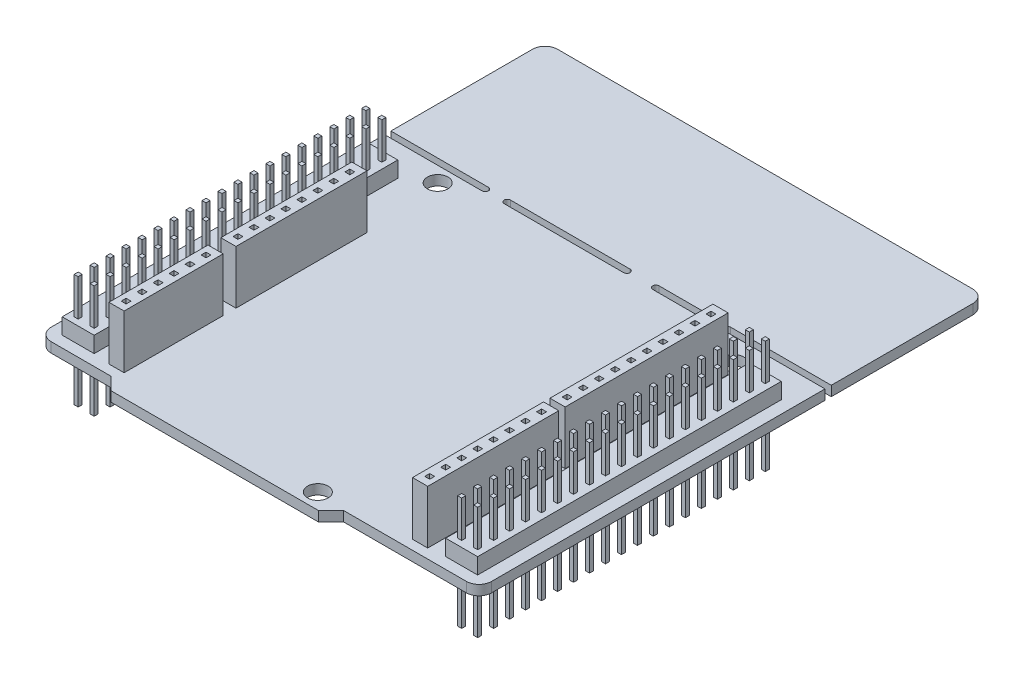
SolidWorks part; units mm, degrees
ref_plane "Front" through (0, 0, 0) normal (0, 0, 1) x (1, 0, 0)
ref_plane "Top" through (0, 0, 0) normal (0, 1, 0) x (1, 0, 0)
ref_plane "Right" through (0, 0, 0) normal (1, 0, 0) x (0, 0, -1)
ref_axis "X" through (-80.9, 0, 0) along (1, 0, 0)
ref_axis "Y" through (0, -50, 0) along (0, 1, 0)
ref_axis "Z" through (0, 0, -80.9) along (0, 0, 1)
sketch "Sketch1" plane through (0, 0, 0) normal (0, 1, 0) x (1, 0, 0)
  line L6 (6.06, 55.5) -> (-1.27, 55.5)
  line L7 (-1.27, 54.5) -> (6.06, 54.5)
  line L10 (-5.89, 55.5) -> (-24.89, 55.5)
  line L11 (-24.89, 54.5) -> (-5.89, 54.5)
  line L53 (24.11, 80) -> (-41.89, 80)
  line L54 (-43.89, 78) -> (-43.89, 55.5)
  line L55 (-43.89, 55.5) -> (-28.39, 55.5)
  line L56 (-28.39, 54.5) -> (-43.89, 54.5)
  line L57 (-43.89, 54.5) -> (-43.89, 1.5)
  line L58 (-41.89, -0.5) -> (-32.39, -0.5)
  line L59 (-32.39, -0.5) -> (-30.39, -2.5)
  line L60 (-30.39, -2.5) -> (2.61, -2.5)
  line L61 (2.61, -2.5) -> (4.61, -0.5)
  line L62 (4.61, -0.5) -> (24.11, -0.5)
  line L63 (26.11, 1.5) -> (26.11, 54.5)
  line L64 (26.11, 54.5) -> (10.11, 54.5)
  line L65 (10.11, 55.5) -> (26.11, 55.5)
  line L66 (26.11, 55.5) -> (26.11, 78)
  arc A21 (1.636, 0) -> (-1.636, 0) centre (0, 0) ccw
  arc A22 (-1.636, 0) -> (1.636, 0) centre (0, 0) ccw
  arc A31 (26.11, 78) -> (24.11, 80) centre (24.11, 78) ccw
  arc A32 (-41.89, 80) -> (-43.89, 78) centre (-41.89, 78) ccw
  arc A33 (-28.39, 54.5) -> (-28.39, 55.5) centre (-28.39, 55) ccw
  arc A34 (-43.89, 1.5) -> (-41.89, -0.5) centre (-41.89, 1.5) ccw
  arc A35 (24.11, -0.5) -> (26.11, 1.5) centre (24.11, 1.5) ccw
  arc A36 (9.61, 55) -> (10.11, 54.5) centre (10.11, 55) ccw
  arc A37 (10.11, 55.5) -> (9.61, 55) centre (10.11, 55) ccw
  arc A39 (16.876, 50.8) -> (13.604, 50.8) centre (15.24, 50.8) ccw
  arc A40 (13.604, 50.8) -> (16.876, 50.8) centre (15.24, 50.8) ccw
  arc A43 (-31.384, 52.07) -> (-34.656, 52.07) centre (-33.02, 52.07) ccw
  arc A44 (-34.656, 52.07) -> (-31.384, 52.07) centre (-33.02, 52.07) ccw
  arc A49 (6.06, 54.5) -> (6.06, 55.5) centre (6.06, 55) ccw
  arc A50 (-1.77, 55) -> (-1.27, 54.5) centre (-1.27, 55) ccw
  arc A51 (-1.27, 55.5) -> (-1.77, 55) centre (-1.27, 55) ccw
  arc A55 (-5.89, 54.5) -> (-5.89, 55.5) centre (-5.89, 55) ccw
  arc A56 (-25.39, 55) -> (-24.89, 54.5) centre (-24.89, 55) ccw
  arc A57 (-24.89, 55.5) -> (-25.39, 55) centre (-24.89, 55) ccw
extrude "Boss-Extrude1" add sketch "Sketch1" along normal mid plane 1.5802
sketch "Sketch2" plane through (0, 0.7901, 0) normal (0, 1, 0) x (1, 0, 0)
  line L0 (-41.9101, 49.5301) -> (-36.8301, 49.5301)
  line L1 (-36.8301, 49.5301) -> (-36.8301, 1.2701)
  line L2 (-36.8301, 1.2701) -> (-41.9101, 1.2701)
  line L3 (-41.9101, 1.2701) -> (-41.9101, 49.5301)
  line L4 (19.0499, 49.5301) -> (24.1299, 49.5301)
  line L5 (24.1299, 49.5301) -> (24.1299, 1.2701)
  line L6 (24.1299, 1.2701) -> (19.0499, 1.2701)
  line L7 (19.0499, 1.2701) -> (19.0499, 49.5301)
  line L8 (-43.89, 54.5) -> (-43.89, 1.5) construction
  line L14 (-41.89, -0.5) -> (-32.39, -0.5) construction
  dimension "D1" = 1.9799
  dimension "D2" = 5.08
  dimension "D3" = 48.26
  dimension "D4" = 55.88
  dimension "D5" = 1.7701
extrude "Boss-Extrude2" add sketch "Sketch2" along normal blind 2.5298
sketch "Sketch3" plane through (0, 3.3199, 0) normal (0, 1, 0) x (1, 0, 0)
  line L0 (-40.9576, 48.5776) -> (-40.3226, 48.5776)
  line L1 (-40.3226, 48.5776) -> (-40.3226, 47.9426)
  line L2 (-40.3226, 47.9426) -> (-40.9576, 47.9426)
  line L3 (-40.9576, 47.9426) -> (-40.9576, 48.5776)
  line L4 (20.0024, 48.5776) -> (20.6374, 48.5776)
  line L5 (20.0024, 48.5776) -> (20.0024, 47.9426)
  line L6 (20.0024, 47.9426) -> (20.6374, 47.9426)
  line L7 (20.6374, 47.9426) -> (20.6374, 48.5776)
  line L8 (-40.9576, 48.2601) -> (-40.6401, 48.2601) construction
  line L9 (-40.6401, 48.2601) -> (-40.6401, 48.5776) construction
  line L10 (20.3199, 48.5776) -> (20.3199, 48.2601) construction
  line L11 (20.3199, 48.2601) -> (20.0024, 48.2601) construction
  line L12 (-36.8301, 49.5301) -> (-41.9101, 49.5301) construction
  line L13 (-41.9101, 49.5301) -> (-41.9101, 1.2701) construction
  line L14 (19.0499, 49.5301) -> (19.0499, 1.2701) construction
  dimension "D1" = 0.635
  dimension "D2" = 1.27
  dimension "D3" = 1.27
  dimension "D4" = 1.27
extrude "Boss-Extrude3" add sketch "Sketch3" along normal blind 5.842 and the other way blind 12.11
pattern_linear "LPattern1" count 2 spacing 2.54 along (1, 0, 0) count 19 spacing 2.54 along (0, 0, 1) of "Boss-Extrude3"
sketch "Sketch4" plane through (0, 0.7901, 0) normal (0, 1, 0) x (1, 0, 0)
  line L0 (-34.2266, 1.0161) -> (-31.8136, 1.0161)
  line L1 (-31.8136, 1.0161) -> (-31.8136, 16.7641)
  line L2 (-31.8136, 39.6241) -> (-34.2266, 39.6241)
  line L3 (-34.2266, 39.6241) -> (-34.2266, 18.7961)
  line L4 (14.0334, 1.0161) -> (16.4464, 1.0161)
  line L5 (16.4464, 1.0161) -> (16.4464, 21.8441)
  line L6 (16.4464, 48.7681) -> (14.0334, 48.7681)
  line L7 (14.0334, 48.7681) -> (14.0334, 22.8601)
  line L8 (-34.2266, 16.7641) -> (-31.8136, 16.7641)
  line L9 (-31.8136, 18.7961) -> (-34.2266, 18.7961)
  line L10 (14.0334, 21.8441) -> (16.4464, 21.8441)
  line L11 (16.4464, 22.8601) -> (14.0334, 22.8601)
  line L12 (-31.8136, 18.7961) -> (-31.8136, 39.6241)
  line L13 (-34.2266, 16.7641) -> (-34.2266, 1.0161)
  line L14 (16.4464, 22.8601) -> (16.4464, 48.7681)
  line L15 (14.0334, 21.8441) -> (14.0334, 1.0161)
  line L16 (-41.9101, 1.2701) -> (-36.8301, 1.2701) construction
  line L17 (-36.8301, 1.2701) -> (-36.8301, 49.5301) construction
  line L18 (19.0499, 49.5301) -> (19.0499, 1.2701) construction
  dimension "D1" = 2.413
  dimension "D2" = 0.254
  dimension "D3" = 2.032
  dimension "D4" = 1.016
  dimension "D5" = 2.6035
  dimension "D6" = 2.6035
  dimension "D7" = 15.748
  dimension "D8" = 20.828
  dimension "D9" = 20.828
  dimension "D10" = 25.908
extrude "Boss-Extrude4" add sketch "Sketch4" along normal blind 8.4988
sketch "Sketch5" plane through (0, 9.2889, 0) normal (0, 1, 0) x (1, 0, 0)
  line L0 (-33.4138, 2.9338) -> (-32.6264, 2.9338)
  line L1 (-32.6264, 2.9338) -> (-32.6264, 2.1464)
  line L2 (-32.6264, 2.1464) -> (-33.4138, 2.1464)
  line L3 (-33.4138, 2.1464) -> (-33.4138, 2.9338)
  line L4 (-33.4138, 2.5401) -> (-33.0201, 2.5401) construction
  line L5 (-33.0201, 2.5401) -> (-33.0201, 2.9338) construction
  line L6 (-33.0201, 2.5401) -> (-33.0201, 1.0161) construction
  line L7 (-34.2266, 1.0161) -> (-31.8136, 1.0161) construction
  point P18 (15.2399, 1.0161)
  point P19 (15.0519, 24.3472)
  point P20 (15.0821, 25.5545)
  point P21 (15.2399, 22.8601)
  dimension "D1" = 0.7874
  dimension "D2" = 1.1303
extrude "Cut-Extrude1" cut sketch "Sketch5" against normal blind 6
pattern_linear "LPattern2" count 18 spacing 2.54 along (0, 0, -1) count 2 spacing 48.26 along (1, 0, 0) skipping (6, 0), (8, 1), (9, 1), (10, 1), (11, 1), (12, 1), (13, 1), (14, 1), (15, 0), (15, 1), (16, 0), (16, 1), (17, 0), (17, 1) of "Cut-Extrude1"
sketch "Sketch7" plane through (0, 9.2889, 0) normal (0, 1, 0) x (1, 0, 0)
  line L0 (14.8462, 24.7778) -> (15.6336, 24.7778)
  line L1 (15.6336, 24.7778) -> (15.6336, 23.9904)
  line L2 (15.6336, 23.9904) -> (14.8462, 23.9904)
  line L3 (14.8462, 23.9904) -> (14.8462, 24.7778)
  line L4 (14.8462, 24.3841) -> (15.2399, 24.3841) construction
  line L5 (15.2399, 24.3841) -> (15.2399, 24.7778) construction
  line L6 (15.2399, 24.3841) -> (15.2399, 22.8601) construction
  line L8 (14.0334, 22.8601) -> (16.4464, 22.8601) construction
  point P6 (15.2399, 22.8601)
  point P18 (62.9199, 23.5852)
  point P19 (62.7318, 46.9163)
  point P20 (62.7621, 48.1236)
  point P21 (62.9199, 45.4292)
  dimension "D1" = 0.7874
  dimension "D2" = 1.1303
extrude "Cut-Extrude2" cut sketch "Sketch7" against normal blind 6
pattern_linear "LPattern3" count 10 spacing 2.54 along (0, 0, -1) of "Cut-Extrude2"
